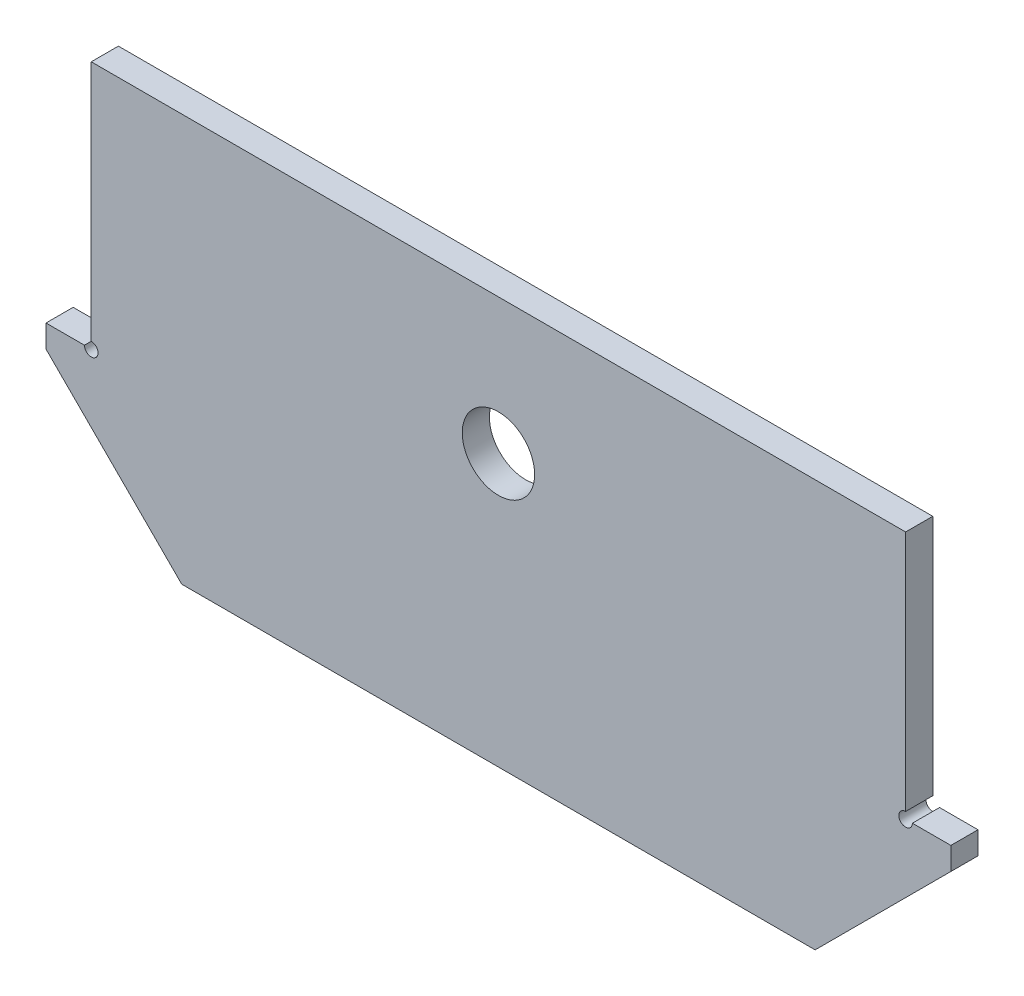
SolidWorks part; units mm, degrees
ref_plane "Front Plane" through (0, 0, 0) normal (0, 0, 1) x (1, 0, 0)
ref_plane "Top Plane" through (0, 0, 0) normal (0, 1, 0) x (1, 0, 0)
ref_plane "Right Plane" through (0, 0, 0) normal (1, 0, 0) x (0, 0, -1)
sketch "Sketch1" plane through (0, 0, 0) normal (0, 0, 1) x (1, 0, 0)
  line L0 (90, -1414) -> (90, -1294) construction
  line L2 (-90, -1414) -> (-90, -1359)
  line L3 (-90, -1359) -> (90, -1359)
  line L4 (90, -1414) -> (90, -1359)
  line L6 (150, -1414) -> (150, -1294) construction
  line L7 (-100, -1414) -> (-90, -1414)
  line L8 (-100, -1414) -> (-100, -1419)
  line L9 (-70, -1449) -> (70, -1449)
  line L10 (100, -1414) -> (100, -1419)
  line L11 (90, -1414) -> (100, -1414)
  line L12 (-100, -1419) -> (-70, -1449)
  line L13 (70, -1449) -> (100, -1419)
  line L14 (-30.8239, -1354) -> (30.8239, -1354) construction
  point P10 (100, -1449)
  point P11 (-100, -1449)
  dimension "D1" = 90
  dimension "D2" = 5
  dimension "D3" = 200
extrude "Boss-Extrude1" add sketch "Sketch1" along normal blind 3 and the other way blind 3
sketch "Sketch2" plane through (0, 0, 3) normal (0, 0, 1) x (1, 0, 0)
  circle A0 centre (0, -1389) radius 8
  point P3 (0, 0)
  dimension "D1" = 16
extrude "Cut-Extrude1" cut sketch "Sketch2" against normal through all both and the other way through all
sketch "Sketch3" plane through (0, 0, 3) normal (0, 0, 1) x (1, 0, 0)
  circle A0 centre (-90, -1414) radius 1.5
  circle A1 centre (90, -1414) radius 1.5
  dimension "D1" = 3
  dimension "D2" = 3
extrude "Cut-Extrude2" cut sketch "Sketch3" against normal through all both and the other way through all
